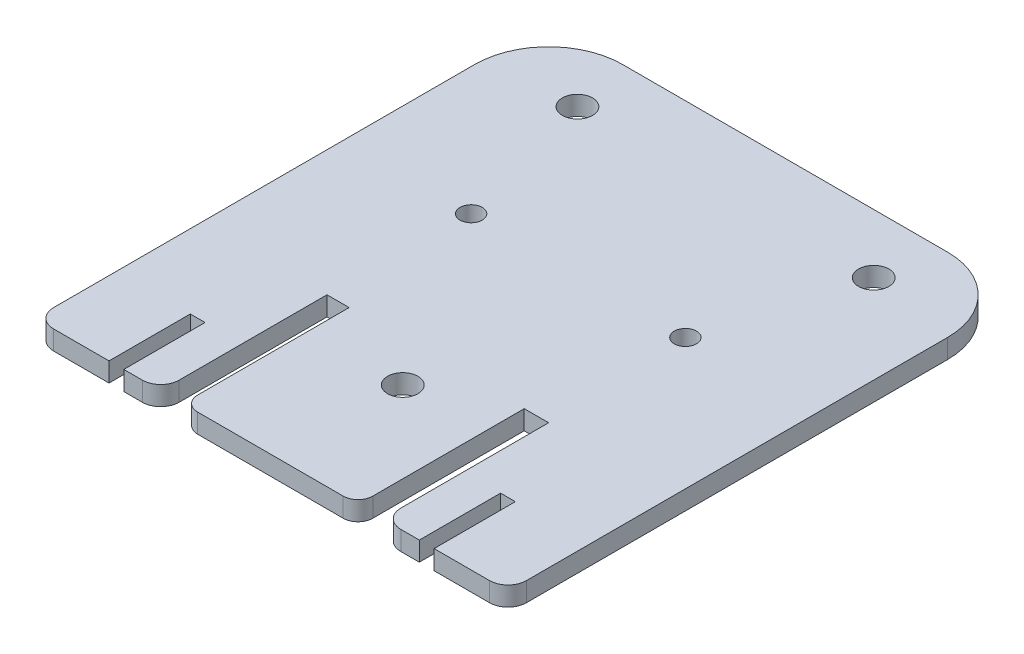
SolidWorks part; units mm, degrees
ref_plane "Front Plane" through (0, 0, 0) normal (0, 0, 1) x (1, 0, 0)
ref_plane "Top Plane" through (0, 0, 0) normal (0, 1, 0) x (1, 0, 0)
ref_plane "Right Plane" through (0, 0, 0) normal (1, 0, 0) x (0, 0, -1)
sketch "Sketch1" plane through (0, 0, 0) normal (0, 1, 0) x (1, 0, 0)
  line L0 (11.7, -23.5) -> (32, -23.5)
  line L1 (-32, -23.5) -> (-12, -23.5)
  line L2 (-32, -23.5) -> (-32, 13.5)
  line L3 (-22, 23.5) -> (22, 23.5)
  line L4 (32, -23.5) -> (32, 13.5)
  line L5 (-32, -23.5) -> (32, 23.5) construction
  line L6 (-32, 23.5) -> (32, -23.5) construction
  line L8 (-12, -23.5) -> (-12, -46)
  line L9 (-12, -46) -> (11.7, -46)
  line L10 (11.7, -23.5) -> (11.7, -46)
  arc A0 (-32, 13.5) -> (-22, 23.5) centre (-22, 13.5) cw
  arc A1 (32, 13.5) -> (22, 23.5) centre (22, 13.5) ccw
  point P0 (0, 0)
  dimension "D6" = 10
  dimension "D7" = 10
  dimension "D1" = 64
  dimension "D2" = 47
  dimension "D3" = 20
  dimension "D4" = 23.7
  dimension "D5" = 22.5
extrude "Main Body" add sketch "Sketch1" along normal blind 2.6
sketch "Sketch2" plane through (0, 2.6, 0) normal (0, 1, 0) x (1, 0, 0)
  line L0 (22, 23.5) -> (-22, 23.5) construction
  line L1 (-32, 13.5) -> (-32, -23.5) construction
  line L2 (0, 0) -> (0, 23.5) construction
  line L3 (32, -23.5) -> (32, 13.5) construction
  line L4 (0.7, -31) -> (0.7, -32.3) construction
  line L5 (0.7, -32.3) -> (14.26, -32.3) construction
  line L6 (-12, -23.5) -> (-12, -46) construction
  line L7 (14.26, -32.3) -> (14.26, -4.25) construction
  line L8 (-14.74, -4.25) -> (-16.24, -4.25) construction
  line L9 (14.26, -4.25) -> (15.76, -4.25) construction
  circle A0 centre (-20.1, 15.5) radius 2.05
  circle A1 centre (20, 15.5) radius 2.05
  circle A3 centre (-14.74, -4.25) radius 1.5
  circle A4 centre (14.26, -4.25) radius 1.5
  circle A6 centre (0.7, -28.95) radius 2.05
  point P21 (0, 0)
  point P23 (8.5, -34.2639)
  point P24 (0, 0)
  point P25 (0, 0)
  point P31 (9.3728, -34.2622)
  point P32 (0, 0)
  point P35 (8.7734, -34.8393)
  dimension "D1" = 4.1
  dimension "D4" = 4.1
  dimension "D7" = 29
  dimension "D8" = 3
  dimension "D9" = 3
  dimension "D10" = 13.56
  dimension "D11" = 4.1
  dimension "D2" = 8
  dimension "D3" = 11.9
  dimension "D5" = 8
  dimension "D6" = 12
  dimension "D12" = 28.05
  dimension "D13" = 1.3
  dimension "D20" = 12.7
  dimension "D21" = 44.45
extrude "Screw holes" cut sketch "Sketch2" against normal through all both and the other way through all
fillet "Main lower body Fillet" radius 2 2 edges at (11.7, 1.3, 46) (-12, 1.3, 46)
sketch "Sketch4" plane through (0, 2.6, 0) normal (0, 1, 0) x (1, 0, 0)
  line L1 (-32, -23.5) -> (-15, -23.5)
  line L2 (-32, -23.5) -> (-32, -21)
  line L3 (-32, -21) -> (-15, -21)
  line L4 (-15, -23.5) -> (-15, -21)
  line L5 (32, -23.5) -> (15, -23.5)
  line L6 (32, -23.5) -> (32, -21)
  line L7 (32, -21) -> (15, -21)
  line L8 (15, -23.5) -> (15, -21)
  dimension "D1" = 2.5
  dimension "D2" = 2.5
  dimension "D3" = 17
  dimension "D4" = 17
sketch "Sketch5" plane through (0, 0, 23.5) normal (0, 0, 1) x (1, 0, 0)
  line L0 (-32, 0) -> (-12, 0) construction
  line L1 (-32, 2.6) -> (-15, 2.6)
  line L2 (-32, 2.6) -> (-32, 0)
  line L3 (-32, 0) -> (-15, 0)
  line L4 (-15, 2.6) -> (-15, 0)
  line L5 (11.7, 0) -> (32, 0) construction
  line L6 (32, 2.6) -> (15, 2.6)
  line L7 (32, 2.6) -> (32, 0)
  line L8 (32, 0) -> (15, 0)
  line L9 (15, 2.6) -> (15, 0)
  dimension "D1" = 17
  dimension "D2" = 17
extrude "Boss-Extrude1" add sketch "Sketch5" along normal blind 22.5
sketch "Sketch6" plane through (0, 2.6, 0) normal (0, 1, 0) x (1, 0, 0)
  line L0 (-15, -46) -> (-32, -46) construction
  line L1 (-20, -46) -> (-22, -46)
  line L2 (-20, -46) -> (-20, -35)
  line L3 (-20, -35) -> (-22, -35)
  line L4 (-22, -46) -> (-22, -35)
  line L5 (32, -46) -> (15, -46) construction
  line L6 (22, -46) -> (20, -46)
  line L7 (22, -46) -> (22, -35)
  line L8 (22, -35) -> (20, -35)
  line L9 (20, -46) -> (20, -35)
  line L10 (-32, 13.5) -> (-32, -46) construction
  line L11 (32, -46) -> (32, 13.5) construction
  point P16 (21, -35)
  dimension "D1" = 12
  dimension "D2" = 12
  dimension "D3" = 10
  dimension "D4" = 10
  dimension "D5" = 11
  dimension "D6" = 11
extrude "Cut-Extrude1" cut sketch "Sketch6" against normal blind 22.5
fillet "Fillet2" radius 2.5 4 edges at (-32, 1.3, 46) (-15, 1.3, 46) (15, 1.3, 46) (32, 1.3, 46)
